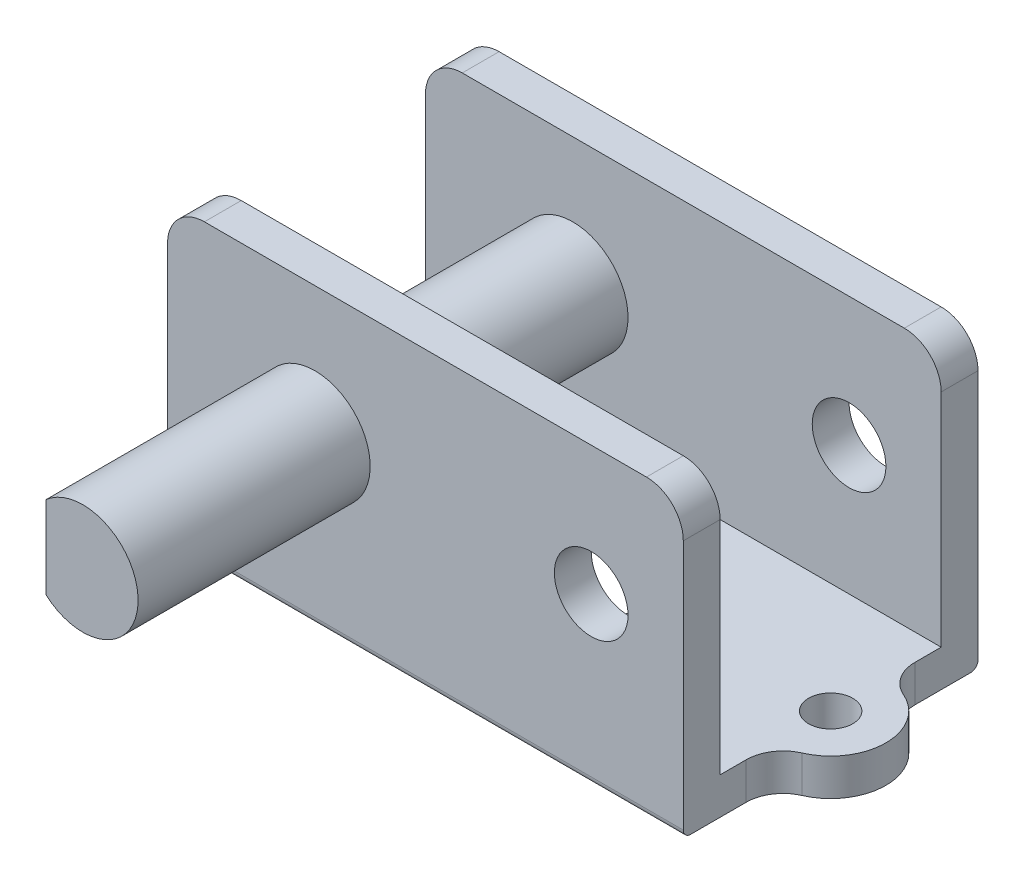
SolidWorks part; units mm, degrees
ref_plane "Спереди" through (0, 0, 0) normal (0, 0, 1) x (1, 0, 0)
ref_plane "Сверху" through (0, 0, 0) normal (0, 1, 0) x (1, 0, 0)
ref_plane "Справа" through (0, 0, 0) normal (1, 0, 0) x (0, 0, -1)
sketch "Sketch1" plane through (0, 0, 0) normal (0, 0, 1) x (1, 0, 0)
  line L0 (0, 0) -> (-7, 0)
  line L1 (-7, 0) -> (-7, 8)
  line L2 (-7, 8) -> (7, 8)
  line L3 (7, 8) -> (7, 0)
  line L4 (7, 0) -> (0, 0)
extrude "Extrude1" add sketch "Sketch1" along normal mid plane 8
sketch "Sketch2" plane through (0, 0, 0) normal (0, 0, 1) x (1, 0, 0)
  line L0 (7, 8) -> (7, 4.5) construction
  line L1 (7, 4.5) -> (4.5, 4.5) construction
  circle A0 centre (4.5, 4.5) radius 1
extrude "Extrude2" cut sketch "Sketch2" against normal through all both and the other way through all
sketch "Sketch3" plane through (0, 0, 0) normal (0, 0, 1) x (1, 0, 0)
  line L0 (-7, 8) -> (-3, 8)
  line L1 (-3, 8) -> (-3, 4.5)
  circle A0 centre (-3, 4.5) radius 1.5
sketch "Sketch4" plane through (0, 0, 0) normal (1, 0, 0) x (0, 0, -1)
  line L0 (0, 0) -> (0, 1)
  line L1 (3, 1) -> (-3, 1)
  line L2 (-3, 1) -> (-3, 9.732)
  line L3 (3, 1) -> (3, 9.732)
  line L4 (-3, 9.732) -> (3, 9.732)
extrude "Extrude3" cut sketch "Sketch4" against normal through all both and the other way through all contours L4 L2 L1 L3 region at (0, 5.366, 0)
fillet "Fillet1" radius 0.2 2 edges at (0, 0, 4) (0, 0, -4)
fillet "Fillet2" radius 1 4 edges at (7, 8, -3.5) (7, 8, 3.5) (-7, 8, -3.5) (-7, 8, 3.5)
extrude "Extrude4" add sketch "Sketch3" along normal blind 14 and the other way blind 3 contours A0 region at (-4.0307, 3.4693, 0)
sketch "Sketch5" plane through (0, 0, 14) normal (0, 0, 1) x (1, 0, 0)
  line L0 (-1.5, 4.5) -> (-4, 4.5)
  line L1 (-4, 4.5) -> (-4, 6.0607)
  line L2 (-4, 6.0607) -> (-4.9564, 6.0607)
  line L3 (-4.9564, 6.0607) -> (-4.9564, 2.5)
  line L4 (-4.9564, 2.5) -> (-4, 2.5)
  line L5 (-4, 2.5) -> (-4, 4.5)
  circle A0 centre (-3, 4.5) radius 1.5 construction
  circle A1 centre (-3, 4.5) radius 1.5 construction
  circle M1 centre (-3, 4.5) radius 1.5
extrude "Extrude5" cut sketch "Sketch5" against normal blind 9 contours L4 L5 L1 L2 L3 M1 | L5 L1 M1 region at (-4.2032, 4.5, 14) region at (-4.5592, 4.2157, 14)
sketch "Sketch6" plane through (0, 0, 0) normal (0, -1, 0) x (1, 0, 0)
  line L0 (0, 0) -> (-8.5, 0)
  line L2 (0, 0) -> (0, 5.5899)
  circle A1 centre (-7, 0) radius 1.5
  circle A2 centre (0, 0) radius 6
  circle A3 centre (7, 0) radius 1.5
  line M12 (-7, 3.8) -> (-7, -3.8)
  line M13 (7, -3.8) -> (7, 3.8)
extrude "Extrude6" add sketch "Sketch6" against normal blind 1 contours L0 A1 | A1 L0 | A3 | A3 M13 | A2 A1 L0 M12 | A2 L0 A1 M12 region at (-6.5089, 0, -0.6972) region at (-6.5089, 0, 0.6972) region at (-7.6366, 0, -0.6366) region at (-7.6366, 0, 0.6366) region at (7.6366, 0, 0)
sketch "Sketch7" plane through (0, 0, 0) normal (0, -1, 0) x (1, 0, 0)
  circle A0 centre (-7, 0) radius 0.6
  circle A1 centre (7, 0) radius 0.6
extrude "Extrude7" cut sketch "Sketch7" against normal blind 1
fillet "Fillet3" radius 1 4 edges at (7, 0.5, -1.5) (7, 0.5, 1.5) (-7, 0.5, -1.5) (-7, 0.5, 1.5)
sketch "Sketch8" plane through (0, 0, 0) normal (0, -1, 0) x (1, 0, 0)
  circle A0 centre (0, 0) radius 2
extrude "Extrude8" cut sketch "Sketch8" against normal blind 1
sketch "Sketch9" plane through (0, 0, 4) normal (0, 0, 1) x (1, 0, 0)
  circle A0 centre (-3, 4.5) radius 2.1726
extrude "Extrude9" cut sketch "Sketch9" along normal blind 10 from offset 6.3
